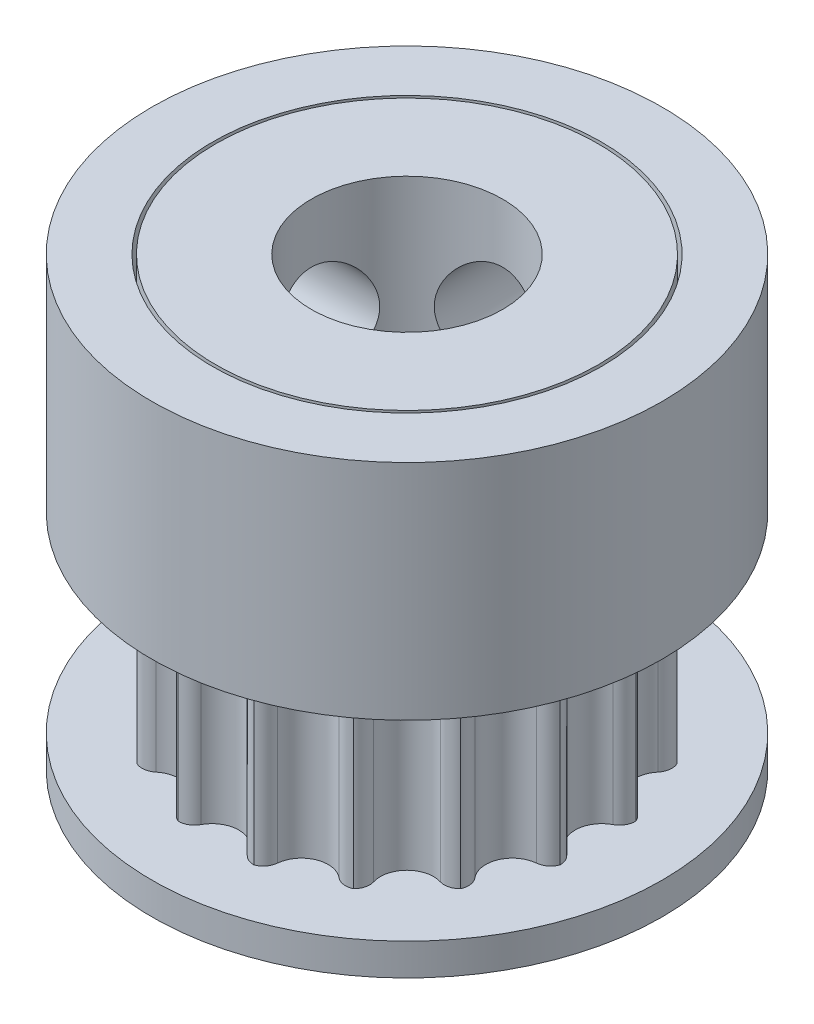
SolidWorks part; units mm, degrees
ref_plane "Front plan" through (0, 0, 0) normal (0, 0, 1) x (1, 0, 0)
ref_plane "Top plan" through (0, 0, 0) normal (0, 1, 0) x (1, 0, 0)
ref_plane "Right plan" through (0, 0, 0) normal (1, 0, 0) x (0, 0, -1)
sketch "Skica2" plane through (0, 0, 0) normal (0, 0, 1) x (1, 0, 0)
  line L0 (8, 7.5) -> (3, 7.5)
  line L1 (3, 7.5) -> (3, -7.5)
  line L2 (3, -7.5) -> (6.11, -7.5)
  line L3 (0, -7.5) -> (0, 7.5) construction
  line L4 (0, 7.5) -> (3, 7.5)
  line L5 (0, -7.5) -> (3, -7.5)
  line L6 (6.11, -7.5) -> (6.11, -6.5)
  line L7 (8, 0.5) -> (6.11, 0.5)
  line L8 (6.11, 0.5) -> (6.11, -5.5)
  line L9 (8, 0.5) -> (8, 7.5)
  line L12 (8, -6.5) -> (6.11, -6.5)
  line L14 (8, -6.5) -> (8, -5.5)
  line L15 (6.11, -5.5) -> (8, -5.5)
  point P6 (7.055, -6.5)
  point P7 (0, 0)
  dimension "D3" = 12.22
  dimension "D1" = 6
  dimension "D2" = 1
  dimension "D4" = 1
  dimension "D5" = 6
  dimension "D6" = 16
  dimension "D8" = 15
revolve "Revolute" add sketch "Skica2" angle 360 about L3 region at (5.1669, 0.6731, 0)
sketch "Sketch2" plane through (0, 0.5, 0) normal (0, -1, 0) x (1, 0, 0)
  line L0 (0, 0) -> (0, 6.11) construction
  line L1 (0, 0) -> (3, 5.3101) construction
  line L2 (0, 0) -> (1.6183, 5.8743) construction
  line L3 (0, 0) -> (-1.6183, 5.8743) construction
  circle A1 centre (0, 0) radius 5.274 construction
  circle A2 centre (0, 0) radius 5.61 construction
  arc A3 (-0.7387, 5.7185) -> (0.7387, 5.7185) centre (0, 6.11) ccw
  circle A4 centre (0, 0) radius 6.11 construction
  circle A5 centre (0, 0) radius 6.11 construction
  arc A7 (2.2516, 5.6827) -> (3.7026, 4.857) centre (3, 5.3101) ccw construction
  arc A8 (0, 7.3117) -> (1.6183, 5.8743) centre (0.4048, 6.1378) cw
  circle A9 centre (0, 0) radius 6.11 construction
  arc A10 (1.2857, 5.9732) -> (1.6218, 5.8908) centre (0, 0) cw
  arc A11 (1.2857, 5.9732) -> (0.7387, 5.7185) centre (1.1804, 5.4844) ccw
  arc A12 (0, 7.3117) -> (-1.6183, 5.8743) centre (-0.4048, 6.1378) ccw
  arc A13 (-1.2857, 5.9732) -> (-0.7387, 5.7185) centre (-1.1804, 5.4844) cw
  point P17 (-0.834, 6.0528)
  point P19 (0.4048, 6.11)
  point P21 (0, 0)
  point P22 (1.5837, 5.9012)
  point P25 (1.4622, 5.8908)
  point P26 (1.2768, 5.9751)
  point P27 (0.7387, 5.6827)
  circle M8 centre (0, 0) radius 6.11
  dimension "D1" = 3
  dimension "D2" = 1
  dimension "D3" = 1.2417
  dimension "D4" = 0.836
  dimension "D5" = 6.11
extrude "Cut-Extrude1" cut sketch "Sketch2" along normal up to surface (6 mm away) contours A8 M8 | A11 A3 M8 region at (0, 0.5, 5.7583) region at (0, 0.5, 6.6333) up to face at (8, -5.5, 0)
pattern_circular "CirPattern1" count 16 over 360 about axis through (0, -7.5, 0) along (0, -1, 0) of "Cut-Extrude1" reverse direction yes
sketch "Sketch3" plane through (0, 0, 0) normal (1, 0, 0) x (0, 0, -1)
  line L0 (0, 7.5) -> (0, 0.5) construction
  line L1 (3, 7.5) -> (-3, 7.5) construction
  line L2 (-0.7387, 0.5) -> (0.7387, 0.5) construction
  circle A0 centre (0, 4) radius 1.65
  dimension "D1" = 3.3
extrude "Cut-Extrude2" cut sketch "Sketch3" against normal up to next
sketch "Sketch4" plane through (0, 0, 0) normal (0, 0, 1) x (1, 0, 0)
  line L0 (0, 7.5) -> (0, 0.5) construction
  line L1 (8, 7.5) -> (-8, 7.5) construction
  line L2 (-0.7387, 0.5) -> (0.7387, 0.5) construction
  circle A0 centre (0, 4) radius 1.65
  dimension "D1" = 3.3
extrude "Cut-Extrude3" cut sketch "Sketch4" against normal up to next
sketch "Sketch5" plane through (0, 7.5, 0) normal (0, 1, 0) x (1, 0, 0)
  circle A0 centre (0, 0) radius 6
  circle A1 centre (0, 0) radius 3 construction
  dimension "D1" = 3
extrude "Cut-Extrude-Thin1" cut sketch "Sketch5" against normal blind 5 thin thin type one direction wall 0.1
chamfer "Chamfer1" distance 1 angle 45 1 edges at (6.11, -6.5, 0)
equation "\"`\"=2"
